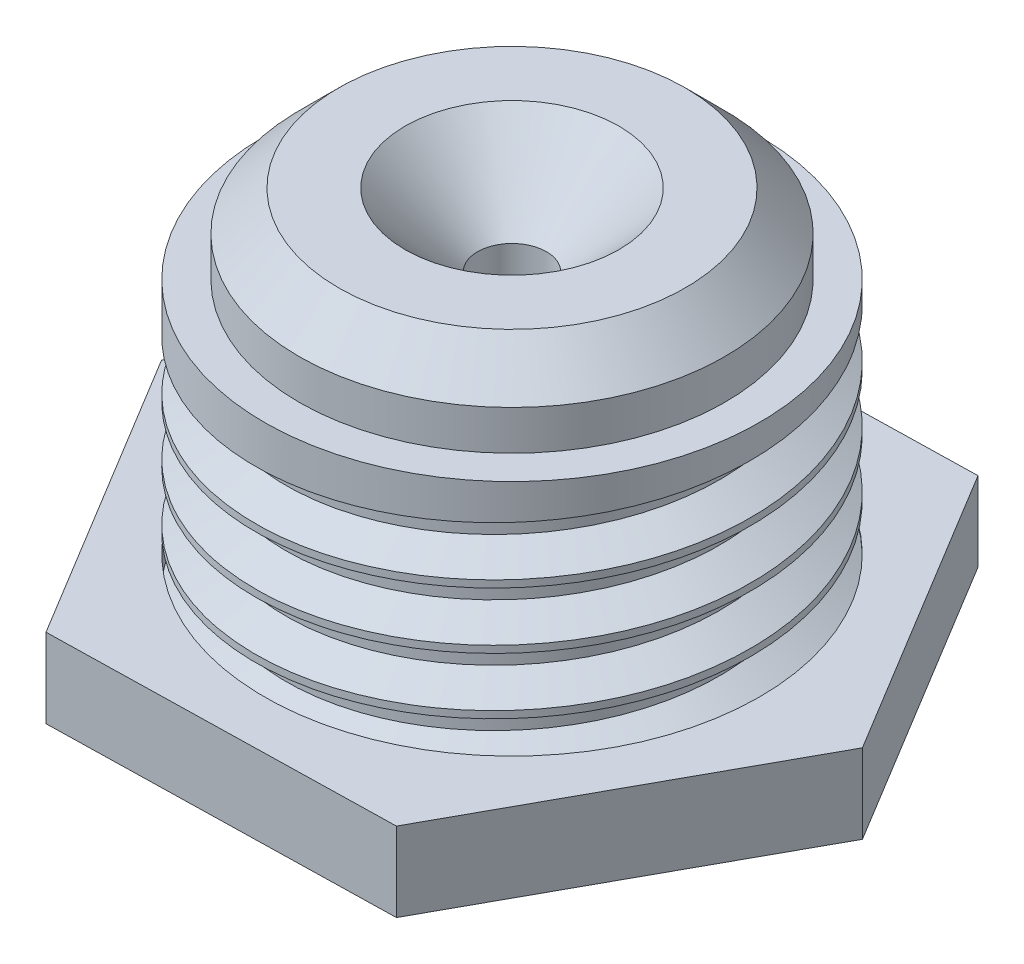
SolidWorks part; units mm, degrees
material "6061-T6 (SS)"
ref_plane "Front Plane" through (0, 0, 0) normal (0, 0, 1) x (1, 0, 0)
ref_plane "Top Plane" through (0, 0, 0) normal (0, 1, 0) x (1, 0, 0)
ref_plane "Right Plane" through (0, 0, 0) normal (1, 0, 0) x (0, 0, -1)
ref_axis "Axis1" through (0, 110.1512, 0) along (0, -1, 0)
sketch "Sketch1" plane through (0, 0, 0) normal (0, 0, 1) x (1, 0, 0)
  line L0 (-15.875, 15.24) -> (-13.6487, 15.24)
  line L1 (-15.875, 0) -> (-15.875, 15.24)
  line L2 (-13.6487, 15.24) -> (-13.6487, 20.32)
  line L3 (-13.6487, 20.32) -> (-6.858, 20.32)
  line L5 (-2.2098, 15.6718) -> (0, 15.6718)
  line L6 (-15.875, 0) -> (0, 0)
  line L8 (0, 110.1512) -> (0, -76.4241) construction
  line L9 (0, 15.6718) -> (0, 0)
  line L10 (-6.858, 20.32) -> (-2.2098, 15.6718)
  dimension "D1" = 15.875
  dimension "D2" = 15.24
  dimension "D3" = 135
  dimension "D4" = 6.858
  dimension "D5" = 13.6487
  dimension "D6" = 2.2098
  dimension "D7" = 5.08
revolve "Revolve1" add sketch "Sketch1" angle 360 about axis through (0, 110.1512, 0) along (0, -1, 0)
cosmetic thread "Cosmetic Thread1" parameters "D2"=27.4295
ref_plane "Plane2" through (0, 110.1512, 0) normal (-1, 0, 0) x (0, 0, 1)
sketch "Sketch12" plane through (0, 0, 0) normal (0, -1, 0) x (1, 0, 0)
  line L1 (-21.992, 0.4698) -> (-11.4029, -18.8107)
  line L2 (-11.4029, -18.8107) -> (10.5891, -19.2806)
  line L3 (10.5891, -19.2806) -> (21.992, -0.4698)
  line L4 (21.992, -0.4698) -> (11.4029, 18.8107)
  line L5 (11.4029, 18.8107) -> (-10.5891, 19.2806)
  line L6 (-10.5891, 19.2806) -> (-21.992, 0.4698)
  circle A0 centre (0, 0) radius 19.05 construction
  dimension "D1" = 38.1
extrude "Boss-Extrude2" add sketch "Sketch12" along normal blind 5.08
sketch "Sketch2" plane through (0, 15.6718, 0) normal (0, 1, 0) x (1, 0, 0)
  circle A0 centre (0, 0) radius 2.2098
extrude "Cut-Extrude2" cut sketch "Sketch2" against normal through all
ref_plane "Plane4" through (0, 110.1512, 0) normal (-1, 0, 0) x (0, 0, 1)
ref_plane "Plane6" through (0, 110.1512, 0) normal (-1, 0, 0) x (0, 0, 1)
chamfer "Chamfer2" distance 2.54 angle 45 1 edges at (0, 20.32, 13.6487)
thread "Thread1" pitch 3.6286 method cut profile "Thread Profile1" start angle 0, offset 0, length 0, pitch 3.6286, diameter 31.75
ref_plane "Plane7" through (-15.875, 15.24, 0) normal (0, 0, 1) x (-1, 0, 0)
sketch "Thread Profile1" plane through (-15.875, 15.24, 0) normal (0, 0, 1) x (-1, 0, 0)
  line L0 (0, 0) -> (0, 3.6286) construction
  line L11 (0, 0) -> (0, 3.175)
  line L12 (0, 3.175) -> (-1.964, 2.0411)
  line L13 (-1.964, 2.0411) -> (-1.964, 1.1339)
  line L15 (-1.964, 1.1339) -> (0, 0)
  line L17 (-1.964, 1.5875) -> (0, 1.5875) construction
  point P2 (0, 0)
  dimension "Pitch" = 3.6286
  dimension "Profile_Angle" = 60
  dimension "Profile_Land" = 0.9071
  dimension "Profile_Height" = 1.964
